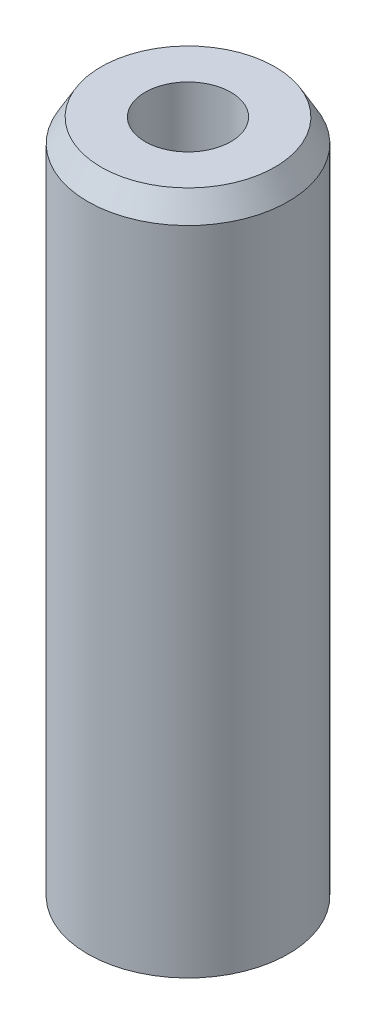
SolidWorks part; units mm, degrees
ref_plane "Front Plane" through (0, 0, 0) normal (0, 0, 1) x (1, 0, 0)
ref_plane "Top Plane" through (0, 0, 0) normal (0, 1, 0) x (1, 0, 0)
ref_plane "Right Plane" through (0, 0, 0) normal (1, 0, 0) x (0, 0, -1)
sketch "Sketch1" plane through (0, 0, 0) normal (0, 1, 0) x (1, 0, 0)
  circle A0 centre (0, 0) radius 10
  dimension "SHAFT_OD" = 20
extrude "Boss-Extrude1" add sketch "Sketch1" along normal blind 68.6099
sketch "Sketch2" plane through (0, 0, 0) normal (0, 1, 0) x (1, 0, 0)
  circle A0 centre (0, 0) radius 4.2753
  dimension "BORE_D" = 8.5506
extrude "Cut-Extrude1" cut sketch "Sketch2" along normal through all
chamfer "Chamfer1" distance 2.3082 angle 30 2 edges at (0, 68.6099, 10) (0, 0, 10) first distance on face at (0, 68.6099, 10) first distance on face at (0, 0, 4.2753)
